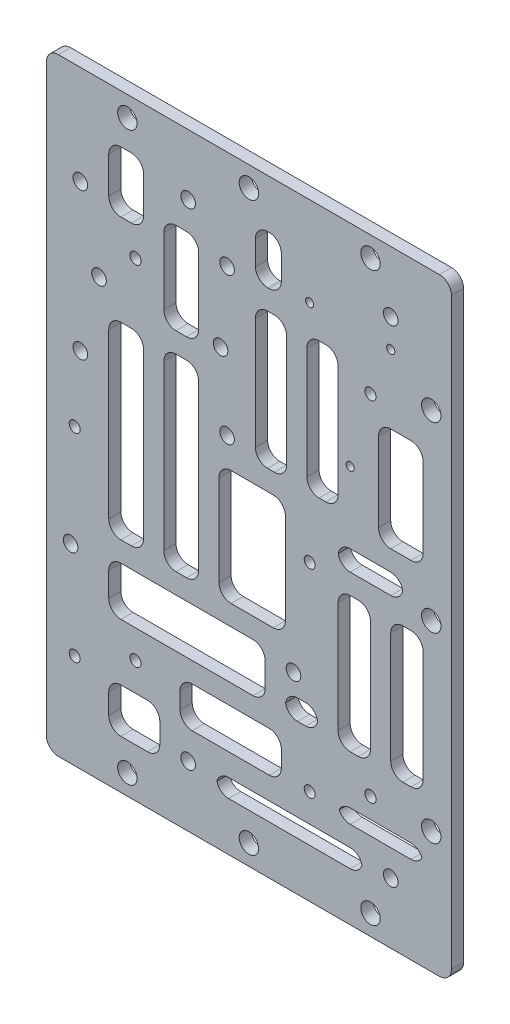
SolidWorks part; units mm, degrees
ref_plane "Plan de face" through (0, 0, 0) normal (0, 0, 1) x (1, 0, 0)
ref_plane "Plan de dessus" through (0, 0, 0) normal (0, 1, 0) x (1, 0, 0)
ref_plane "Plan de droite" through (0, 0, 0) normal (1, 0, 0) x (0, 0, -1)
sketch "Esquisse1" plane through (0, 0, 0) normal (0, 0, 1) x (1, 0, 0)
  line L0 (0, 0) -> (0, 150)
  line L1 (0, 0) -> (100, 0)
  line L2 (0, 150) -> (100, 150)
  line L3 (100, 0) -> (100, 150)
  dimension "D1" = 100
  dimension "D2" = 150
extrude "Boss.-Extru.1" add sketch "Esquisse1" along normal blind 3
sketch "Esquisse2" plane through (0, 0, 3) normal (0, 0, 1) x (1, 0, 0)
  line L0 (0, 0) -> (100, 0) construction
  line L1 (0, 150) -> (0, 0) construction
  line L2 (3.24, 120) -> (84, 120) construction
  line L3 (84, 120) -> (84, 20) construction
  line L4 (84, 20) -> (3.24, 20) construction
  line L5 (3.24, 20) -> (3.24, 120) construction
  circle A0 centre (22, 116) radius 1.375
  circle A1 centre (80, 116) radius 1.375
  circle A2 centre (80, 30) radius 1.375
  circle A3 centre (22, 30) radius 1.375
  dimension "D1" = 2.75
  dimension "D2" = 2.75
  dimension "D3" = 2.75
  dimension "D4" = 2.75
  dimension "D14" = 4
  dimension "D5" = 86
  dimension "D6" = 86
  dimension "D7" = 30
  dimension "D8" = 30
  dimension "D9" = 58
  dimension "D10" = 58
  dimension "D11" = 22
  dimension "D12" = 22
  dimension "D13" = 4
  dimension "D15" = 10
  dimension "D16" = 80.76
extrude "Enlèv. mat.-Extru.1" cut sketch "Esquisse2" against normal blind 3
sketch "Esquisse3" plane through (0, 0, 3) normal (0, 0, 1) x (1, 0, 0)
  line L0 (0, 0) -> (100, 0) construction
  line L1 (100, 0) -> (100, 150) construction
  line L2 (100, 150) -> (0, 150) construction
  line L3 (0, 150) -> (0, 0) construction
  line L4 (100, 75) -> (0, 75) construction
  line L5 (50, 150) -> (50, 0) construction
  circle A0 centre (20, 145) radius 2.4
  circle A1 centre (50, 145) radius 2.4
  circle A2 centre (80, 145) radius 2.4
  circle A3 centre (95, 120) radius 2.4
  circle A4 centre (95, 75) radius 2.4
  circle A5 centre (95, 30) radius 2.4
  circle A6 centre (80, 5) radius 2.4
  circle A7 centre (50, 5) radius 2.4
  circle A8 centre (20, 5) radius 2.4
  circle A11 centre (85, 135) radius 1.8
  circle A12 centre (35, 135) radius 1.8
  circle A13 centre (35, 15) radius 1.8
  circle A14 centre (85, 15) radius 1.8
  dimension "D1" = 4.8
  dimension "D2" = 4.8
  dimension "D3" = 4.8
  dimension "D4" = 4.8
  dimension "D5" = 4.8
  dimension "D6" = 4.8
  dimension "D7" = 4.8
  dimension "D8" = 4.8
  dimension "D9" = 4.8
  dimension "D12" = 5
  dimension "D15" = 5
  dimension "D16" = 5
  dimension "D17" = 5
  dimension "D18" = 5
  dimension "D26" = 30
  dimension "D27" = 30
  dimension "D28" = 3.6
  dimension "D29" = 3.6
  dimension "D32" = 3.6
  dimension "D33" = 3.6
  dimension "D10" = 5
  dimension "D11" = 5
  dimension "D13" = 5
  dimension "D14" = 5
  dimension "D20" = 30
  dimension "D21" = 30
  dimension "D22" = 30
  dimension "D23" = 30
  dimension "D34" = 50
  dimension "D35" = 15
  dimension "D36" = 15
  dimension "D37" = 15
  dimension "D38" = 15
  dimension "D39" = 15
  dimension "D40" = 50
  dimension "D41" = 15
extrude "Enlèv. mat.-Extru.2" cut sketch "Esquisse3" against normal blind 3
sketch "Esquisse4" plane through (0, 0, 3) normal (0, 0, 1) x (1, 0, 0)
  line L0 (100, 0) -> (100, 150) construction
  line L2 (5, 129) -> (5, 86) construction
  line L3 (5, 86) -> (48, 86) construction
  line L4 (48, 86) -> (48, 129) construction
  line L5 (48, 129) -> (5, 129) construction
  line L6 (0, 150) -> (0, 0) construction
  line L7 (100, 150) -> (0, 150) construction
  line L8 (8.4, 125.6) -> (44.6, 125.6) construction
  line L9 (44.6, 125.6) -> (44.6, 89.4) construction
  line L10 (8.4, 89.4) -> (8.4, 125.6) construction
  line L11 (8.4, 89.4) -> (44.6, 89.4) construction
  line L12 (26.5, 129) -> (26.5, 125.6) construction
  line L13 (8.4, 107.5) -> (5, 107.5) construction
  line L14 (85, 79) -> (85, 15) construction
  line L15 (85, 15) -> (-9, 15) construction
  line L16 (-9, 15) -> (-9, 79) construction
  line L17 (-9, 79) -> (85, 79) construction
  line L18 (6, 47) -> (-9, 47) construction
  line L19 (0, 0) -> (100, 0) construction
  line L20 (-9, 47) -> (85, 47) construction
  circle A0 centre (13, 107.5) radius 1.8
  circle A1 centre (44.6, 89.4) radius 1.8
  circle A2 centre (6, 47) radius 1.8
  circle A3 centre (61, 47) radius 1.8
  circle A4 centre (8.4, 125.6) radius 1.8
  circle A5 centre (44.6, 125.6) radius 1.8
  circle A6 centre (85, 128) radius 1
  circle A7 centre (65, 128) radius 1
  circle A8 centre (75, 98) radius 1
  circle A11 centre (8.4, 89.4) radius 1.8
  circle A12 centre (43, 107.5) radius 1.8
  dimension "D1" = 3.6
  dimension "D2" = 3.6
  dimension "D6" = 3.6
  dimension "D7" = 3.6
  dimension "D8" = 3.6
  dimension "D9" = 3.6
  dimension "D10" = 3.6
  dimension "D11" = 3.6
  dimension "D19" = 2
  dimension "D20" = 2
  dimension "D21" = 2
  dimension "D22" = 94
  dimension "D3" = 55
  dimension "D4" = 15
  dimension "D5" = 64
  dimension "D12" = 43
  dimension "D13" = 43
  dimension "D14" = 21
  dimension "D15" = 5
  dimension "D16" = 36.2
  dimension "D17" = 15
  dimension "D18" = 36.2
  dimension "D24" = 15
  dimension "D26" = 21.5
  dimension "D27" = 21.5
  dimension "D28" = 5
  dimension "D29" = 30
  dimension "D30" = 15
  dimension "D31" = 20
  dimension "D32" = 30
  dimension "D33" = 30
  dimension "D34" = 10
  dimension "D35" = 22
extrude "Enlèv. mat.-Extru.3" cut sketch "Esquisse4" against normal blind 10
sketch "Esquisse5" plane through (0, 0, 3) normal (0, 0, 1) x (1, 0, 0)
  line L0 (-8, 76) -> (-8, 20) construction
  line L1 (-8, 20) -> (80, 20) construction
  line L2 (80, 20) -> (80, 76) construction
  line L3 (80, 76) -> (-8, 76) construction
  line L4 (-8, 72.5) -> (80, 72.5) construction
  line L5 (-8, 72.5) -> (7, 76) construction
  line L6 (-8, 23.5) -> (80, 23.5) construction
  line L7 (65, 76) -> (80, 72.5) construction
  line L8 (65, 20) -> (65, 76) construction
  line L9 (80, 23.5) -> (65, 20) construction
  line L10 (7, 20) -> (7, 76) construction
  line L11 (100, 0) -> (100, 150) construction
  line L12 (-8, 23.5) -> (7, 20) construction
  line L13 (0, 0) -> (100, 0) construction
  circle A0 centre (7, 72.5) radius 1.35
  circle A1 centre (65, 72.5) radius 1.35
  circle A2 centre (7, 23.5) radius 1.35
  circle A3 centre (65, 23.5) radius 1.35
  dimension "D1" = 2.7
  dimension "D2" = 2.7
  dimension "D3" = 2.7
  dimension "D4" = 2.7
  dimension "D5" = 56
  dimension "D6" = 88
  dimension "D7" = 49
  dimension "D8" = 58
  dimension "D9" = 20
  dimension "D10" = 20
extrude "Enlèv. mat.-Extru.4" cut sketch "Esquisse5" against normal blind 10
sketch "Esquisse6" plane through (0, 0, 3) normal (0, 0, 1) x (1, 0, 0)
  line L0 (15.4, 100.5) -> (24, 100.5)
  line L1 (15.4, 100.5) -> (15.4, 54)
  line L2 (24, 100.5) -> (24, 54)
  line L3 (15.4, 54) -> (24, 54)
  line L4 (29, 100.5) -> (37.6, 100.5)
  line L5 (29, 100.5) -> (29, 54)
  line L6 (37.6, 100.5) -> (37.6, 54)
  line L7 (29, 54) -> (37.6, 54)
  line L8 (15.4, 49) -> (15.4, 37)
  line L9 (15.4, 49) -> (54, 49)
  line L10 (15.4, 37) -> (54, 37)
  line L11 (54, 49) -> (54, 37)
  line L12 (33, 32) -> (33, 22)
  line L13 (33, 32) -> (58, 32)
  line L14 (33, 22) -> (58, 22)
  line L15 (58, 32) -> (58, 22)
  line L16 (42.6, 82.4) -> (59, 82.4)
  line L17 (42.6, 82.4) -> (42.6, 54)
  line L18 (59, 82.4) -> (59, 54)
  line L19 (42.6, 54) -> (59, 54)
  line L20 (72, 70.4) -> (72, 37)
  line L21 (72, 70.4) -> (80, 70.4)
  line L22 (72, 37) -> (80, 37)
  line L23 (80, 70.4) -> (80, 37)
  line L24 (85, 70.4) -> (85, 37)
  line L25 (85, 70.4) -> (93, 70.4)
  line L26 (85, 37) -> (93, 37)
  line L27 (93, 70.4) -> (93, 37)
  line L28 (51.6, 121) -> (51.6, 87.4)
  line L29 (51.6, 121) -> (59.3, 121)
  line L30 (51.6, 87.4) -> (59.3, 87.4)
  line L31 (59.3, 121) -> (59.3, 87.4)
  line L32 (64.3, 121) -> (64.3, 87.4)
  line L33 (64.3, 121) -> (72, 121)
  line L34 (64.3, 87.4) -> (72, 87.4)
  line L35 (72, 121) -> (72, 87.4)
  line L36 (82, 111) -> (82, 85.4)
  line L37 (82, 111) -> (93, 111)
  line L38 (82, 85.4) -> (93, 85.4)
  line L39 (93, 111) -> (93, 85.4)
  line L40 (72, 80.4) -> (72, 75.4)
  line L41 (72, 80.4) -> (88, 80.4)
  line L42 (72, 75.4) -> (88, 75.4)
  line L43 (88, 80.4) -> (88, 75.4)
  line L44 (42, 16.5) -> (42, 12)
  line L45 (42, 16.5) -> (78, 16.5)
  line L46 (42, 12) -> (78, 12)
  line L47 (78, 16.5) -> (78, 12)
  line L48 (59, 42) -> (59, 37)
  line L49 (59, 42) -> (67, 42)
  line L50 (59, 37) -> (67, 37)
  line L51 (67, 42) -> (67, 37)
  line L52 (72, 25) -> (72, 21.5)
  line L53 (72, 25) -> (93, 25)
  line L54 (72, 21.5) -> (93, 21.5)
  line L55 (93, 25) -> (93, 21.5)
  line L56 (29, 128) -> (29, 105.5)
  line L57 (29, 128) -> (37.6, 128)
  line L58 (29, 105.5) -> (37.6, 105.5)
  line L59 (37.6, 128) -> (37.6, 105.5)
  line L60 (51.6, 138) -> (51.6, 126)
  line L61 (51.6, 138) -> (58, 138)
  line L62 (51.6, 126) -> (58, 126)
  line L63 (58, 138) -> (58, 126)
  line L76 (15.4, 138) -> (24, 138)
  line L77 (15.4, 138) -> (15.4, 123)
  line L78 (24, 138) -> (24, 123)
  line L79 (15.4, 123) -> (24, 123)
  line L80 (15.4, 23) -> (15.4, 12)
  line L81 (15.4, 23) -> (28, 23)
  line L82 (15.4, 12) -> (28, 12)
  line L83 (28, 23) -> (28, 12)
  line L84 (100, 0) -> (100, 150) construction
  circle A0 centre (20, 145) radius 2.4 construction
  circle A1 centre (8.4, 89.4) radius 1.8 construction
  circle A2 centre (20, 5) radius 2.4 construction
  circle A3 centre (65, 23.5) radius 1.35 construction
  circle A4 centre (61, 47) radius 1.8 construction
  circle A5 centre (35, 15) radius 1.8 construction
  circle A6 centre (80, 30) radius 1.375 construction
  circle A7 centre (22, 30) radius 1.375 construction
  circle A8 centre (65, 72.5) radius 1.35 construction
  circle A9 centre (35, 135) radius 1.8 construction
  circle A10 centre (44.6, 125.6) radius 1.8 construction
  circle A11 centre (22, 116) radius 1.375 construction
  circle A12 centre (65, 128) radius 1 construction
  circle A15 centre (44.6, 89.4) radius 1.8 construction
  circle A16 centre (75, 98) radius 1 construction
  circle A17 centre (80, 116) radius 1.375 construction
  circle A18 centre (95, 75) radius 2.4 construction
  circle A19 centre (85, 15) radius 1.8 construction
  circle A20 centre (13, 107.5) radius 1.8 construction
  point P69 (33.3, 100.5)
  dimension "D1" = 7
  dimension "D2" = 7
  dimension "D16" = 7
  dimension "D18" = 5
  dimension "D30" = 7
  dimension "D39" = 7
  dimension "D41" = 7
  dimension "D52" = 7
  dimension "D3" = 7
  dimension "D4" = 7
  dimension "D5" = 5
  dimension "D6" = 5
  dimension "D7" = 5
  dimension "D8" = 5
  dimension "D9" = 5
  dimension "D10" = 5
  dimension "D11" = 5
  dimension "D12" = 7
  dimension "D13" = 7
  dimension "D14" = 5
  dimension "D15" = 7
  dimension "D17" = 5
  dimension "D19" = 7
  dimension "D20" = 7
  dimension "D21" = 7
  dimension "D22" = 5
  dimension "D23" = 5
  dimension "D24" = 5
  dimension "D25" = 5
  dimension "D26" = 7
  dimension "D27" = 5
  dimension "D28" = 5
  dimension "D29" = 5
  dimension "D31" = 7
  dimension "D32" = 5
  dimension "D33" = 7
  dimension "D34" = 7
  dimension "D35" = 5
  dimension "D36" = 7
  dimension "D37" = 7
  dimension "D38" = 7
  dimension "D40" = 7
  dimension "D42" = 5
  dimension "D43" = 7
  dimension "D44" = 7
  dimension "D45" = 5
  dimension "D46" = 7
  dimension "D47" = 7
  dimension "D48" = 5
  dimension "D49" = 7
  dimension "D50" = 7
  dimension "D51" = 7
  dimension "D53" = 7
extrude "Enlèv. mat.-Extru.5" cut sketch "Esquisse6" against normal blind 10
fillet "Congé1" radius 3 76 edges at (28, 23, 1.5) (93, 25, 1.5) (78, 16.5, 1.5) (58, 32, 1.5) (67, 42, 1.5) (59.3, 121, 1.5) (37.6, 128, 1.5) (24, 138, 1.5) (24, 100.5, 1.5) (37.6, 100.5, 1.5) (54, 49, 1.5) (93, 70.4, 1.5) (80, 70.4, 1.5) (59, 82.4, 1.5) (72, 121, 1.5) (58, 138, 1.5) (72, 75.4, 1.5) (82, 85.4, 1.5) (64.3, 87.4, 1.5) (51.6, 126, 1.5) (51.6, 87.4, 1.5) (29, 105.5, 1.5) (15.4, 123, 1.5) (15.4, 54, 1.5) (29, 54, 1.5) (42.6, 54, 1.5) (85, 37, 1.5) (59, 37, 1.5) (72, 37, 1.5) (72, 21.5, 1.5) (33, 22, 1.5) (15.4, 37, 1.5) (42, 12, 1.5) (15.4, 12, 1.5) (42, 16.5, 1.5) (15.4, 23, 1.5) (33, 32, 1.5) (15.4, 49, 1.5) (59, 42, 1.5) (72, 25, 1.5) (85, 70.4, 1.5) (72, 80.4, 1.5) (72, 70.4, 1.5) (29, 100.5, 1.5) (42.6, 82.4, 1.5) (15.4, 100.5, 1.5) (29, 128, 1.5) (82, 111, 1.5) (64.3, 121, 1.5) (51.6, 121, 1.5) (51.6, 138, 1.5) (15.4, 138, 1.5) (28, 12, 1.5) (58, 126, 1.5) (24, 123, 1.5) (59.3, 87.4, 1.5) (37.6, 105.5, 1.5) (24, 54, 1.5) (37.6, 54, 1.5) (54, 37, 1.5) (58, 22, 1.5) (59, 54, 1.5) (67, 37, 1.5) (78, 12, 1.5) (93, 21.5, 1.5) (80, 37, 1.5) (93, 37, 1.5) (93, 85.4, 1.5) (72, 87.4, 1.5) (88, 75.4, 1.5) (88, 80.4, 1.5) (93, 111, 1.5) (0, 150, 1.5) (100, 150, 1.5) (100, 0, 1.5) (0, 0, 1.5)
